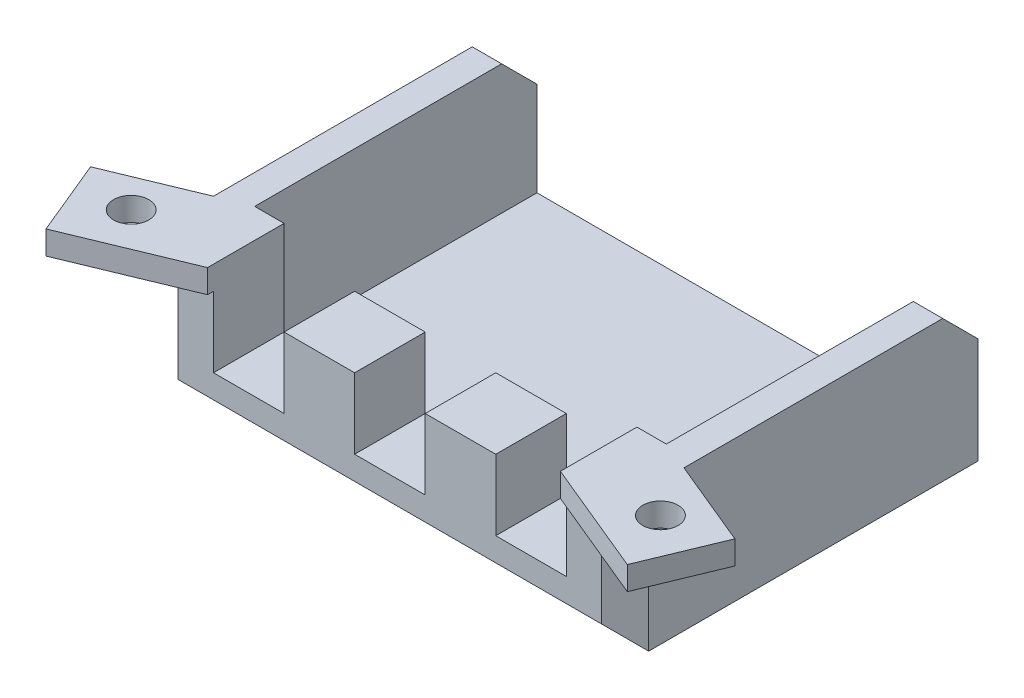
SolidWorks part; units mm, degrees
ref_plane "Front Plane" through (0, 0, 0) normal (0, 0, 1) x (1, 0, 0)
ref_plane "Top Plane" through (0, 0, 0) normal (0, 1, 0) x (1, 0, 0)
ref_plane "Right Plane" through (0, 0, 0) normal (1, 0, 0) x (0, 0, -1)
sketch "Sketch1" plane through (0, 0, 0) normal (0, 1, 0) x (1, 0, 0)
  line L1 (-20, -15) -> (20, -15)
  line L2 (-20, -15) -> (-20, 15)
  line L3 (-20, 15) -> (20, 15)
  line L4 (20, -15) -> (20, 15)
  line L5 (-20, -15) -> (20, 15) construction
  line L6 (-20, 15) -> (20, -15) construction
  point P0 (0, 0)
  dimension "D1" = 40
  dimension "D2" = 30
extrude "Boss-Extrude1" add sketch "Sketch1" along normal blind 10
sketch "Sketch5" plane through (0, 10, 0) normal (0, 1, 0) x (1, 0, 0)
  line L0 (-20, 15) -> (-20, -15) construction
  line L1 (-20, 12) -> (20, 12)
  line L2 (-20, 12) -> (-20, -15)
  line L3 (-20, -15) -> (20, -15)
  line L4 (20, 12) -> (20, -15)
  line L5 (20, 15) -> (-20, 15) construction
  dimension "D1" = 3
extrude "Boss-Extrude2" add sketch "Sketch5" along normal blind 3
sketch "Sketch2" plane through (0, 13, 0) normal (0, 1, 0) x (1, 0, 0)
  line L0 (20, 15) -> (-20, 15) construction
  line L1 (-17.5, 15) -> (-6.5, 15)
  line L2 (-17.5, 15) -> (-17.5, -9)
  line L3 (-17.5, -9) -> (-6.5, -9)
  line L4 (-6.5, 15) -> (-6.5, -9)
  line L5 (-20, 15) -> (-20, 12) construction
  line L6 (-5.5, 15) -> (5.5, 15)
  line L7 (-5.5, 15) -> (-5.5, -9)
  line L8 (-5.5, -9) -> (5.5, -9)
  line L9 (5.5, 15) -> (5.5, -9)
  line L10 (6.5, 15) -> (17.5, 15)
  line L11 (6.5, 15) -> (6.5, -9)
  line L12 (6.5, -9) -> (17.5, -9)
  line L13 (17.5, 15) -> (17.5, -9)
  line L14 (20, 12) -> (20, 15) construction
  line L15 (-20, -15) -> (20, -15) construction
  dimension "D1" = 2.5
  dimension "D2" = 1
  dimension "D3" = 1
  dimension "D4" = 2.5
  dimension "D5" = 6
extrude "Cut-Extrude1" cut sketch "Sketch2" against normal blind 11
sketch "Sketch4" plane through (0, 13, 0) normal (0, 1, 0) x (1, 0, 0)
  line L0 (-17.5, -9) -> (-6.5, -9) construction
  line L1 (-15, -9) -> (-9, -9)
  line L2 (-15, -9) -> (-15, -15)
  line L3 (-15, -15) -> (-9, -15)
  line L4 (-9, -9) -> (-9, -15)
  line L5 (-20, -15) -> (20, -15) construction
  line L6 (-5.5, -9) -> (5.5, -9) construction
  line L7 (-3, -9) -> (3, -9)
  line L8 (-3, -9) -> (-3, -15)
  line L9 (-3, -15) -> (3, -15)
  line L10 (3, -9) -> (3, -15)
  line L16 (6.5, -9) -> (17.5, -9) construction
  line L17 (9, -9) -> (15, -9)
  line L18 (9, -9) -> (9, -15)
  line L19 (9, -15) -> (15, -15)
  line L20 (15, -9) -> (15, -15)
  line L21 (17.5, 15) -> (6.5, 15) construction
  line L22 (-6.5, 15) -> (-17.5, 15) construction
  point P22 (12, 15)
  point P23 (12, -9)
  point P24 (0, -9)
  point P28 (-12, 15)
  point P29 (-12, -9)
  dimension "D1" = 6
extrude "Cut-Extrude2" cut sketch "Sketch4" against normal blind 8
sketch "Sketch6" plane through (0, 13, 0) normal (0, 1, 0) x (1, 0, 0)
  line L0 (9, -9) -> (9, -15) construction
  line L1 (-9, -15) -> (9, -15)
  line L2 (-9, -15) -> (-9, 1)
  line L3 (-9, 1) -> (9, 1)
  line L4 (9, -15) -> (9, 1)
  dimension "D1" = 16
extrude "Cut-Extrude3" cut sketch "Sketch6" against normal blind 2
chamfer "Chamfer2" distance 3 angle 45 4 edges at (18.75, 10, -12) (6, 10, -12) (-6, 10, -12) (-18.75, 10, -12)
sketch "Sketch8" plane through (0, 13, 0) normal (0, 1, 0) x (1, 0, 0)
  line L0 (20, -10) -> (27.391, -13.0615)
  line L1 (20, -15) -> (20, 12) construction
  line L4 (15, -15) -> (20, -15) construction
  line L6 (15, -15) -> (17.5, -9)
  line L7 (17.5, -9) -> (20, -10)
  line L8 (15, -15) -> (15, -15.5057)
  line L9 (15, -15.5057) -> (24.7123, -19.5286)
  line L10 (27.391, -13.0615) -> (24.7123, -19.5286)
  line L11 (9, -15) -> (15, -15) construction
  dimension "D1" = 157.5
  dimension "D2" = 25
  dimension "D3" = 7
  dimension "D4" = 8
extrude "Boss-Extrude3" add sketch "Sketch8" against normal blind 2
mirror "Mirror1" about plane through (0, 0, 0) normal (1, 0, 0) of "Boss-Extrude3"
sketch "Sketch9" plane through (0, 11, 0) normal (0, -1, 0) x (1, 0, 0)
  line L0 (0, 0) -> (0, 14.5) construction
  line L1 (-22.5, 14.5) -> (22.5, 14.5) construction
  circle A0 centre (-22.5, 14.5) radius 1.5
  circle A1 centre (22.5, 14.5) radius 1.5
  point P6 (0, 14.5)
  dimension "D3" = 3
  dimension "D1" = 14.5
  dimension "D2" = 45
extrude "Cut-Extrude5" cut sketch "Sketch9" against normal up to vertex (2 mm away) up to point (17.5, 13, 9)
sketch "Sketch11" plane through (0, 0, 0) normal (0, -1, 0) x (1, 0, 0)
  line L1 (-20, 15) -> (20, 15)
  line L2 (-20, 15) -> (-20, -15)
  line L3 (-20, -15) -> (20, -15)
  line L4 (20, 15) -> (20, -15)
extrude "Cut-Extrude6" cut sketch "Sketch11" against normal blind 1
chamfer "Chamfer3" distance 2 angle 45 3 edges at (-20, 6, 15) (20, 6, 15) (0, 1, 15)
sketch "Sketch14" plane through (0, 1, 0) normal (0, -1, 0) x (1, 0, 0)
  line L0 (-20, -15) -> (20, -15) construction
  line L1 (-3, -15) -> (3, -15)
  line L2 (-3, -15) -> (-3, -13)
  line L3 (-3, -13) -> (3, -13)
  line L4 (3, -15) -> (3, -13)
  point P6 (0, -13)
  dimension "D1" = 6
  dimension "D2" = 2
extrude "Boss-Extrude4" add sketch "Sketch14" along normal blind 4
sketch "Sketch15" plane through (0, 0, -15) normal (0, 0, -1) x (-1, 0, 0)
  line L0 (-3, 1) -> (-20, 1) construction
  circle A1 centre (0, -0.5) radius 1.5
  dimension "D2" = 3
  dimension "D1" = 1.5
extrude "Cut-Extrude7" cut sketch "Sketch15" against normal blind 4
chamfer "Chamfer7" distance 4 angle 45 2 edges at (3, 1, -14) (-3, 1, -14)
sketch "Sketch16" plane through (0, 13, 0) normal (0, 1, 0) x (1, 0, 0)
  line L0 (-6.5, -9) -> (-6.5, 15) construction
  line L1 (-6.5, 8.5) -> (6.5, 8.5)
  line L2 (-6.5, 8.5) -> (-6.5, 15)
  line L3 (-6.5, 15) -> (6.5, 15)
  line L4 (6.5, 8.5) -> (6.5, 15)
  dimension "D1" = 6.5
extrude "Cut-Extrude8" cut sketch "Sketch16" against normal blind 3
sketch "Sketch17" plane through (0, 13, 0) normal (0, 1, 0) x (1, 0, 0)
  line L0 (17.5, -9) -> (17.5, 12) construction
  line L1 (-17.5, 15) -> (17.5, 15)
  line L2 (-17.5, 15) -> (-17.5, -9)
  line L3 (-17.5, -9) -> (17.5, -9)
  line L4 (17.5, 15) -> (17.5, -9)
  line L5 (6.5, -9) -> (9, -9) construction
extrude "Cut-Extrude9" cut sketch "Sketch17" against normal up to surface (11 mm away) contours L2 L1 L4 L3 up to face at (-12, 2, -3)
